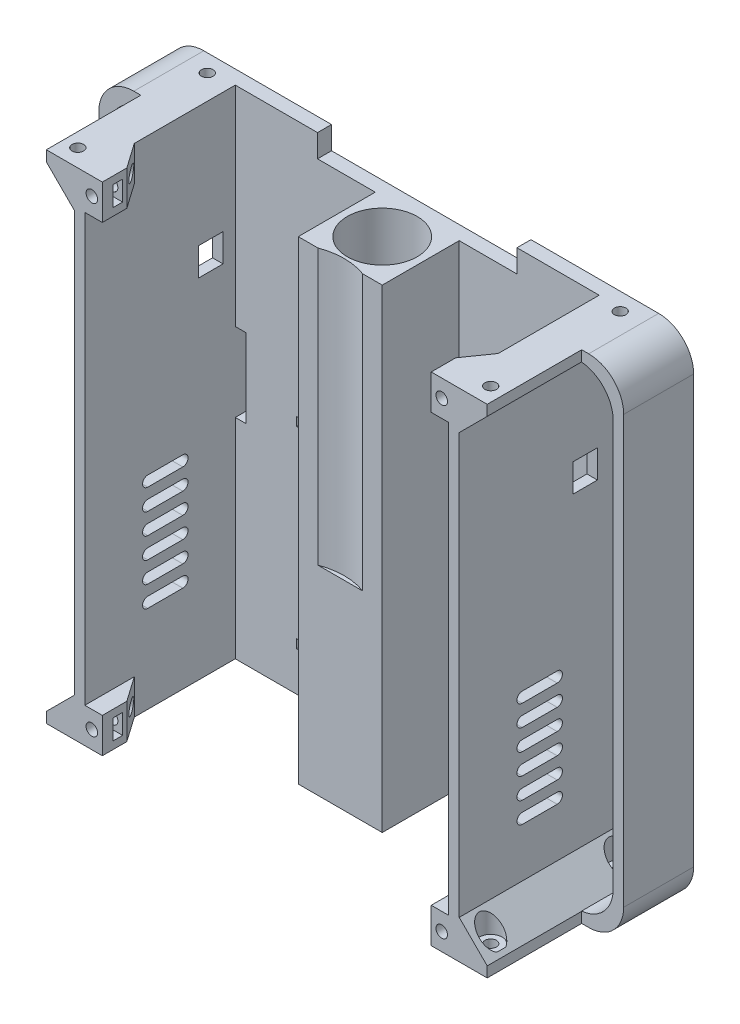
SolidWorks part; units mm, degrees
material "ABS"
ref_plane "Front Plane" through (0, 0, 0) normal (0, 0, 1) x (1, 0, 0)
ref_plane "Top Plane" through (0, 0, 0) normal (0, 1, 0) x (1, 0, 0)
ref_plane "Right Plane" through (0, 0, 0) normal (1, 0, 0) x (0, 0, -1)
sketch "Sketch1" plane through (0, 0, 0) normal (0, 0, 1) x (1, 0, 0)
  line L0 (-42, 71) -> (-42, 67)
  line L1 (-55, 71) -> (55, 71)
  line L2 (-55, 71) -> (-55, -71)
  line L3 (-55, -71) -> (55, -71)
  line L4 (55, 71) -> (55, -71)
  line L5 (-55, 71) -> (55, -71) construction
  line L6 (-55, -71) -> (55, 71) construction
  line L7 (-42, 67) -> (-52, 67)
  line L8 (-52, 71) -> (-52, -71)
  line L9 (-52, -67) -> (-42, -67)
  line L10 (-42, -67) -> (-42, -71)
  line L11 (42, -71) -> (42, -67)
  line L12 (42, -67) -> (52, -67)
  line L13 (52, -71) -> (52, 71)
  line L14 (52, 67) -> (42, 67)
  line L15 (42, 67) -> (42, 71)
  point P0 (0, 0)
  dimension "D2" = 142
  dimension "D3" = 10
  dimension "D4" = 10
  dimension "D5" = 3
  dimension "D6" = 3
  dimension "D7" = 4
  dimension "D8" = 4
  dimension "D9" = 4
  dimension "D10" = 4
  dimension "D11" = 10
  dimension "D12" = 10
  dimension "D13" = 104
extrude "Boss-Extrude1" add sketch "Sketch1" against normal blind 4 contours L14 L15 L1 L0 L7 L8 L9 L10 L3 L11 L12 L13 | L10 L9 L8 L7 L0 L1 L2 L3 | L15 L14 L13 L12 L11 L3 L4 L1 | L15 L14 L13 L1 | L1 L8 L7 L0 | L10 L9 L8 L3 | L3 L13 L12 L11 region at (0, 0, 0) region at (-47, 69, 0) region at (-53.5, 0, 0) region at (47, 69, 0) region at (53.5, 0, 0) region at (-47, -69, 0) region at (47, -69, 0)
extrude "Boss-Extrude2" add sketch "Sketch1<3>" along normal blind 43 contours L10 L9 L8 L7 L0 L1 L2 L3 | L15 L14 L13 L12 L11 L3 L4 L1 region at (-53.5, 0, 0) region at (53.5, 0, 0)
sketch "Sketch1<3>" plane through (0, 0, 0) normal (0, 0, 1) x (1, 0, 0) same geometry as "Sketch1"
sketch "Sketch2" plane through (0, 0, 0) normal (0, 0, 1) x (1, 0, 0)
  line L0 (-52, 71) -> (52, 71) construction
  line L1 (-10.5, -67) -> (-7.5, -67)
  line L2 (-10.5, -67) -> (-10.5, 71)
  line L3 (-10.5, 71) -> (-7.5, 71)
  line L4 (-7.5, -67) -> (-7.5, 71)
  line L5 (-10.5, -67) -> (-7.5, 71) construction
  line L6 (-10.5, 71) -> (-7.5, -67) construction
  line L8 (7.5, -67) -> (10.5, -67)
  line L9 (7.5, -67) -> (7.5, 71)
  line L10 (7.5, 71) -> (10.5, 71)
  line L11 (10.5, -67) -> (10.5, 71)
  line L12 (7.5, -67) -> (10.5, 71) construction
  line L13 (7.5, 71) -> (10.5, -67) construction
  point P0 (-9, 2)
  point P7 (9, 2)
  dimension "D1" = 3
  dimension "D2" = 3
  dimension "D3" = 7.5
  dimension "D4" = 15
extrude "Boss-Extrude3" [suppressed] add sketch "Sketch2" along normal blind 20
chamfer "Chamfer2" [suppressed] distance 0.5 angle 45
sketch "Sketch8" plane through (0, 0, 0) normal (0, 0, 1) x (1, 0, 0)
  line L0 (-52, -71) -> (52, -71) construction
  line L1 (10, -71) -> (12, -71)
  line L2 (10, -71) -> (10, 71)
  line L3 (10, 71) -> (12, 71)
  line L4 (12, -71) -> (12, 71)
  line L5 (-52, 71) -> (52, 71) construction
  line L7 (-10, -71) -> (-12, -71)
  line L8 (-10, -71) -> (-10, 71)
  line L9 (-10, 71) -> (-12, 71)
  line L10 (-12, -71) -> (-12, 71)
  dimension "D1" = 2
  dimension "D2" = 2
  dimension "D3" = 10
  dimension "D4" = 10
sketch "Sketch11" plane through (0, 0, 43) normal (0, 0, 1) x (1, 0, 0)
  line L0 (55, 71) -> (63, 71)
  line L1 (63, 71) -> (63, 68)
  line L2 (63, 68) -> (55, 60)
  line L3 (55, 71) -> (55, -71) construction
  line L4 (55, 60) -> (55, 71)
  dimension "D1" = 3
  dimension "D2" = 8
  dimension "D3" = 11
extrude "Boss-Extrude10" add sketch "Sketch11" against normal up to surface (47 mm away) up to face at (0, 0, -4)
sketch "Sketch12" plane through (0, 71, 0) normal (0, 1, 0) x (1, 0, 0)
  line L0 (63, 4) -> (63, -43) construction
  line L1 (52, -43) -> (63, -43) construction
  circle A0 centre (59, -38) radius 1.65
  circle A1 centre (59, -38) radius 3.25
  circle A2 centre (59, -1) radius 1.65
  circle A3 centre (59, -1) radius 3.25
  dimension "D1" = 3.3
  dimension "D2" = 6.5
  dimension "D5" = 3.3
  dimension "D6" = 6.5
  dimension "D3" = 4
  dimension "D4" = 5
  dimension "D7" = 37
extrude "Cut-Extrude3" cut sketch "Sketch12" against normal blind 14 contours A0 | A2 region at (59, 71, 38) region at (59, 71, 1)
extrude "Cut-Extrude4" cut sketch "Sketch12<3>" against normal blind 14 from offset 4 offset against normal yes
sketch "Sketch12<3>" plane through (0, 71, 0) normal (0, 1, 0) x (1, 0, 0) same geometry as "Sketch12"
sketch "Sketch13" plane through (0, 71, 0) normal (0, 1, 0) x (1, 0, 0)
  line L0 (52, -43) -> (47, -43)
  line L1 (47, -43) -> (47, -36)
  line L2 (47, -36) -> (52, -28.8593)
  line L3 (52, -43) -> (52, 0) construction
  line L4 (52, -28.8593) -> (52, -43)
  dimension "D1" = 5
  dimension "D2" = 7
  dimension "D3" = 35
extrude "Boss-Extrude11" add sketch "Sketch13" against normal blind 10
sketch "Sketch14" plane through (0, 0, 43) normal (0, 0, 1) x (1, 0, 0)
  line L0 (47, 61) -> (47, 71) construction
  line L1 (47, 71) -> (63, 71) construction
  line L3 (47, 68.85) -> (53.5, 68.85)
  line L4 (47, 68.85) -> (47, 63.15)
  line L5 (47, 63.15) -> (53.5, 63.15)
  line L6 (53.5, 68.85) -> (53.5, 63.15)
  circle A0 centre (50, 66) radius 1.65
  point P11 (53.5, 66)
  dimension "D3" = 3.3
  dimension "D1" = 3
  dimension "D2" = 5
  dimension "D4" = 5.7
  dimension "D5" = 6.5
extrude "Cut-Extrude5" cut sketch "Sketch14" against normal blind 18 contours A0 region at (50, 66, 43)
extrude "Cut-Extrude6" cut sketch "Sketch14<3>" against normal blind 2.8 from offset 3 offset against normal yes
sketch "Sketch14<3>" plane through (0, 0, 43) normal (0, 0, 1) x (1, 0, 0) same geometry as "Sketch14"
mirror "Mirror1" about plane through (0, 0, 0) normal (0, 1, 0) of "Cut-Extrude6", "Cut-Extrude5", "Boss-Extrude11", "Boss-Extrude10", "Cut-Extrude3", "Cut-Extrude4"
mirror "Mirror2" about plane through (0, 0, 0) normal (1, 0, 0) of "Cut-Extrude6", "Cut-Extrude5", "Boss-Extrude11", "Boss-Extrude10", "Cut-Extrude3", "Cut-Extrude4", "Mirror1"
sketch "Sketch17" plane through (0, -71, 0) normal (0, -1, 0) x (1, 0, 0)
  line L1 (-52, 0) -> (52, 0) construction
  line L2 (-9.99, 10) -> (-9.99, 0)
  line L3 (-9.99, 0) -> (-12, 0)
  line L4 (-12, 0) -> (-12, 10)
  line L5 (9.99, 10) -> (9.99, 0)
  line L6 (9.99, 0) -> (12, 0)
  line L7 (12, 0) -> (12, 10)
  line L8 (-9.99, 0) -> (9.99, 0)
  line L9 (12, 10) -> (9.99, 10)
  line L10 (0, 0.01) -> (0, 0)
  line L11 (-12, 10) -> (-12, 22)
  line L12 (-12, 22) -> (12, 22)
  line L13 (12, 22) -> (12, 10)
  circle A0 centre (0, 10) radius 9.99
  arc A1 (-12, 10) -> (12, 10) centre (0, 10) cw
  point P8 (0, 0)
  line M5 (52, 0) -> (-52, 0)
  dimension "D1" = 19.98
  dimension "D2" = 12
  dimension "D3" = 10
extrude "Boss-Extrude12" add sketch "Sketch17" against normal up to surface (142 mm away) contours A1 L4 L2 A0 L5 L7 M5 | A0 L2 L8 | A0 L5 L7 L9 M5 | L11 A1 L12 | L12 A1 L13 | A0 L10 L5 M5 region at (-7.7457, -71, 2.2311) region at (-10.3156, -71, 5) region at (10.995, -71, 5) region at (7.7457, -71, 2.2311) region at (9.3196, -71, 19.3196) region at (-9.3196, -71, 19.3196) up to face at (-59, 71, 39.65)
sketch "Sketch18" plane through (0, 0, 0) normal (0, 0, 1) x (1, 0, 0)
  line L0 (-52, -71) -> (-12, -71) construction
  line L1 (-34.5, -57.25) -> (-29.5, -57.25)
  line L2 (-34.5, -57.25) -> (-34.5, -59.75)
  line L3 (-34.5, -59.75) -> (-29.5, -59.75)
  line L4 (-29.5, -57.25) -> (-29.5, -59.75)
  line L5 (-34.5, -57.25) -> (-29.5, -59.75) construction
  line L6 (-34.5, -59.75) -> (-29.5, -57.25) construction
  line L7 (-34.5, -2.25) -> (-29.5, -2.25)
  line L8 (-34.5, -2.25) -> (-34.5, -4.75)
  line L9 (-34.5, -4.75) -> (-29.5, -4.75)
  line L10 (-29.5, -2.25) -> (-29.5, -4.75)
  line L11 (-34.5, -2.25) -> (-29.5, -4.75) construction
  line L12 (-34.5, -4.75) -> (-29.5, -2.25) construction
  line L13 (52, -71) -> (52, 71) construction
  line L14 (12, -11.25) -> (15, -11.25)
  line L15 (12, -11.25) -> (12, 11.25)
  line L16 (12, 11.25) -> (15, 11.25)
  line L17 (15, -11.25) -> (15, 11.25)
  line L18 (12, -11.25) -> (15, 11.25) construction
  line L19 (12, 11.25) -> (15, -11.25) construction
  line L20 (49, -11.25) -> (52, -11.25)
  line L21 (49, -11.25) -> (49, 11.25)
  line L22 (49, 11.25) -> (52, 11.25)
  line L23 (52, -11.25) -> (52, 11.25)
  line L24 (49, -11.25) -> (52, 11.25) construction
  line L25 (49, 11.25) -> (52, -11.25) construction
  line L26 (12, -71) -> (12, 71) construction
  point P0 (-32, -58.5)
  point P5 (-32, -3.5)
  point P10 (50.5, 0)
  point P14 (13.5, 0)
  point P31 (-32, -71)
  dimension "D1" = 12.5
  dimension "D2" = 52.5
  dimension "D3" = 2.5
  dimension "D4" = 5
  dimension "D5" = 22.5
  dimension "D6" = 3
extrude "Cut-Extrude7" cut sketch "Sketch18" against normal blind 15.1
sketch "Sketch19" plane through (0, 71, 0) normal (0, 1, 0) x (1, 0, 0)
  line L1 (-52, 0) -> (-12, 0) construction
  line L2 (-63, 4) -> (63, 4) construction
  circle A0 centre (0, -39.35) radius 18.5
  point P7 (0, 4)
  dimension "D2" = 37
  dimension "D1" = 39.35
extrude "Cut-Extrude8" cut sketch "Sketch19" against normal blind 85
sketch "Sketch20" plane through (0, 0, -4) normal (0, 0, -1) x (-1, 0, 0)
  line L0 (63, 71) -> (-63, 71) construction
  line L1 (-28.5, 64.5) -> (28.5, 64.5)
  line L2 (-28.5, 64.5) -> (-28.5, 71)
  line L3 (-28.5, 71) -> (28.5, 71)
  line L4 (28.5, 64.5) -> (28.5, 71)
  line L5 (-28.5, 64.5) -> (28.5, 71) construction
  line L6 (-28.5, 71) -> (28.5, 64.5) construction
  point P0 (0, 67.75)
  dimension "D1" = 57
  dimension "D2" = 6.5
extrude "Cut-Extrude9" cut sketch "Sketch20" against normal blind 47
mirror "Mirror3" about plane through (0, 0, 0) normal (1, 0, 0) of "Cut-Extrude7"
sketch "Sketch21" plane through (-55, 0, 0) normal (-1, 0, 0) x (0, 0, 1)
  line L0 (25, -44.5) -> (15, -44.5) construction
  line L1 (25, -46) -> (15, -46)
  line L2 (25, -43) -> (15, -43)
  line L3 (-4, 60) -> (-4, -60) construction
  line L4 (-4, -71) -> (43, -71) construction
  line L5 (25, -38.5) -> (15, -38.5) construction
  line L6 (25, -40) -> (15, -40)
  line L7 (25, -37) -> (15, -37)
  line L8 (25, -32.5) -> (15, -32.5) construction
  line L9 (25, -34) -> (15, -34)
  line L10 (25, -31) -> (15, -31)
  line L11 (25, -26.5) -> (15, -26.5) construction
  line L12 (25, -28) -> (15, -28)
  line L13 (25, -25) -> (15, -25)
  line L14 (25, -20.5) -> (15, -20.5) construction
  line L15 (25, -22) -> (15, -22)
  line L16 (25, -19) -> (15, -19)
  line L17 (25, -14.5) -> (15, -14.5) construction
  line L18 (25, -16) -> (15, -16)
  line L19 (25, -13) -> (15, -13)
  arc A0 (25, -46) -> (25, -43) centre (25, -44.5) ccw
  arc A1 (15, -43) -> (15, -46) centre (15, -44.5) ccw
  arc A2 (25, -40) -> (25, -37) centre (25, -38.5) ccw
  arc A3 (15, -37) -> (15, -40) centre (15, -38.5) ccw
  arc A4 (25, -34) -> (25, -31) centre (25, -32.5) ccw
  arc A5 (15, -31) -> (15, -34) centre (15, -32.5) ccw
  arc A6 (25, -28) -> (25, -25) centre (25, -26.5) ccw
  arc A7 (15, -25) -> (15, -28) centre (15, -26.5) ccw
  arc A8 (25, -22) -> (25, -19) centre (25, -20.5) ccw
  arc A9 (15, -19) -> (15, -22) centre (15, -20.5) ccw
  arc A10 (25, -16) -> (25, -13) centre (25, -14.5) ccw
  arc A11 (15, -13) -> (15, -16) centre (15, -14.5) ccw
  point P2 (20, -44.5)
  point P15 (20, -38.5)
  point P22 (20, -32.5)
  point P29 (20, -26.5)
  point P36 (20, -20.5)
  point P41 (20, -14.5)
  dimension "D1" = 10
  dimension "D2" = 3
  dimension "D3" = 19
  dimension "D4" = 25
  dimension "D5" = 6
extrude "Cut-Extrude10" cut sketch "Sketch21" against normal blind 10
mirror "Mirror4" about plane through (0, 0, 0) normal (1, 0, 0) of "Cut-Extrude10"
sketch "Sketch22" plane through (55, 0, 0) normal (1, 0, 0) x (0, 0, -1)
  line L1 (4, 60) -> (-43, 60) construction
  line L2 (-16.5, -13) -> (-16.5, 60) construction
  line L3 (4, 60) -> (4, -60) construction
  text T1 "<b>STORM</b>" font "Sofachrome Rg" height 7
  dimension "D1" = 20.5
extrude "Boss-Extrude13" [suppressed] add sketch "Sketch22" along normal blind 0.5
sketch "Sketch23" plane through (-55, 0, 0) normal (-1, 0, 0) x (0, 0, 1)
  line L0 (16.5, -13) -> (16.5, 60) construction
  line L5 (-4, 60) -> (43, 60) construction
  line L7 (-4, 60) -> (-4, -60) construction
  text T1 "<b>STORM</b>" font "Sofachrome Rg" height 7
  dimension "D2" = 20.5
extrude "Boss-Extrude14" [suppressed] add sketch "Sketch23" along normal blind 0.5
sketch "Sketch24" plane through (-52, 0, 0) normal (1, 0, 0) x (0, 0, -1)
  line L0 (0, 71) -> (0, 11.25) construction
  line L1 (-14, 19) -> (0, 19) construction
  line L2 (-14, 19) -> (-14, 46) construction
  line L3 (-14, 46) -> (0, 46) construction
  line L4 (0, 19) -> (0, 46) construction
  line L5 (-28.8593, 71) -> (0, 71) construction
  line L6 (0, 46) -> (-14, 19) construction
  line L7 (-14, 46) -> (0, 19) construction
  line L9 (-3.5, 36.5) -> (-10.5, 36.5)
  line L10 (-3.5, 36.5) -> (-3.5, 28.5)
  line L11 (-3.5, 28.5) -> (-10.5, 28.5)
  line L12 (-10.5, 36.5) -> (-10.5, 28.5)
  line L13 (-3.5, 36.5) -> (-10.5, 28.5) construction
  line L14 (-3.5, 28.5) -> (-10.5, 36.5) construction
  point P9 (-7, 32.5)
  point P15 (-7, 32.5)
  dimension "D1" = 14
  dimension "D2" = 27
  dimension "D3" = 25
  dimension "D4" = 7.75
  dimension "D5" = 7
  dimension "D6" = 8
  dimension "D7" = 7
extrude "Cut-Extrude12" cut sketch "Sketch24" against normal blind 15
mirror "Mirror5" about plane through (0, 0, 0) normal (1, 0, 0) of "Cut-Extrude12"
sketch "Sketch25" plane through (0, 0, -4) normal (0, 0, -1) x (-1, 0, 0)
  line L0 (63, 68) -> (62, 68)
  line L1 (72, 58) -> (72, -58)
  line L2 (62, -68) -> (63, -68)
  line L3 (63, -68) -> (63, -71)
  line L4 (63, -71) -> (65, -71)
  line L5 (75, -61) -> (75, 61)
  line L6 (65, 71) -> (63, 71)
  line L8 (63, 71) -> (63, 68)
  line L9 (55, 60) -> (55, -60) construction
  arc A0 (75, 61) -> (65, 71) centre (65, 61) ccw
  arc A1 (65, -71) -> (75, -61) centre (65, -61) ccw
  arc A2 (72, -58) -> (62, -68) centre (62, -58) cw
  arc A3 (62, 68) -> (72, 58) centre (62, 58) cw
  point P20 (72, 68)
  dimension "D3" = 10
  dimension "D4" = 10
  dimension "D5" = 10
  dimension "D6" = 10
  dimension "D1" = 17
  dimension "D2" = 3
extrude "Boss-Extrude15" add sketch "Sketch25" against normal blind 20
mirror "Mirror6" about plane through (0, 0, 0) normal (1, 0, 0) of "Boss-Extrude15"
equation "\"D8@Sketch1\"=\"D7@Sketch1\""
equation "\"D4@Sketch1\"=\"D3@Sketch1\""
equation "\"D5@Sketch1\"=\"D6@Sketch1\""
equation "\"D9@Sketch1\"=\"D7@Sketch1\""
equation "\"D10@Sketch1\"=\"D7@Sketch1\""
equation "\"D11@Sketch1\"=\"D3@Sketch1\""
equation "\"D12@Sketch1\"=\"D3@Sketch1\""
equation "\"D3@Sketch2\"=\"D4@Sketch2\"/2"
equation "\"D2@Sketch2\"=\"D1@Sketch2\""
